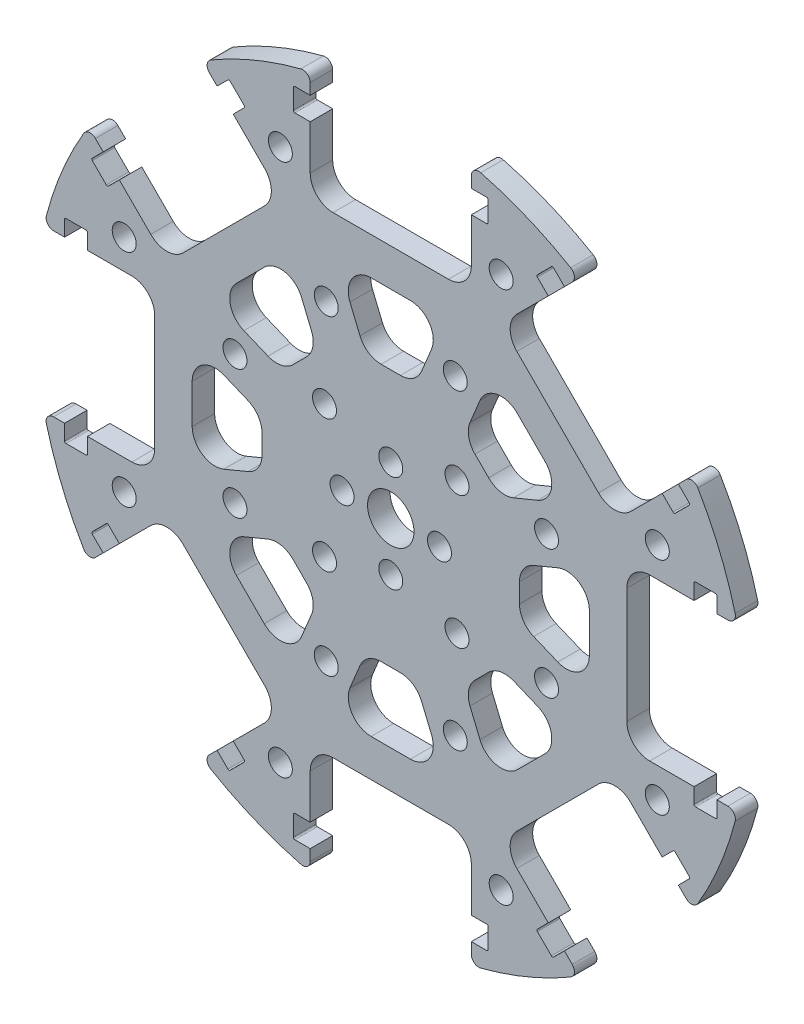
SolidWorks part; units mm, degrees
note: '?' marks a value the reader was unsure of.
material "5052-H34"
ref_plane "正面" through (0, 0, 0) normal (0, 0, 1) x (1, 0, 0)
ref_plane "平面" through (0, 0, 0) normal (0, 1, 0) x (1, 0, 0)
ref_plane "右側面" through (0, 0, 0) normal (1, 0, 0) x (0, 0, -1)
sketch "ｽｹｯﾁ1" plane through (0, 0, 0) normal (0, 0, 1) x (1, 0, 0)
  circle A0 centre (0, 0) radius 47.5
  dimension "D1" = 95
extrude "ﾎﾞｽ - 押し出し1" add sketch "ｽｹｯﾁ1" along normal blind 3
sketch "ｽｹｯﾁ2" plane through (0, 0, 3) normal (0, 0, 1) x (1, 0, 0)
  line L0 (0, 0) -> (0, 47.5) construction
  line L1 (-10.75, 43.525) -> (-10.75, 52.5)
  line L2 (-10.75, 31.5) -> (10.75, 31.5)
  line L3 (-10.75, 31.5) -> (-10.75, 40.475)
  line L4 (-10.75, 52.5) -> (10.75, 52.5)
  line L5 (10.75, 31.5) -> (10.75, 40.475)
  line L6 (-10.75, 31.5) -> (10.75, 52.5) construction
  line L7 (-10.75, 52.5) -> (10.75, 31.5) construction
  line L8 (-13, 43.525) -> (-10.75, 43.525)
  line L9 (-13, 43.525) -> (-13, 40.475)
  line L10 (-13, 40.475) -> (-10.75, 40.475)
  line L11 (13, 43.525) -> (13, 40.475)
  line L12 (-13, 43.525) -> (13, 40.475) construction
  line L13 (-13, 40.475) -> (13, 43.525) construction
  line L14 (10.75, 43.525) -> (10.75, 52.5)
  line L15 (10.75, 43.525) -> (13, 43.525)
  line L17 (10.75, 40.475) -> (13, 40.475)
  circle A0 centre (0, 0) radius 47.5 construction
  point P5 (0, 42)
  point P10 (0, 42)
  dimension "D1" = 42
  dimension "D2" = 21.5
  dimension "D3" = 21
  dimension "D4" = 3.05
  dimension "D5" = 26
extrude "ｶｯﾄ - 押し出し1" cut sketch "ｽｹｯﾁ2" against normal through all
sketch "ｽｹｯﾁ3" plane through (0, 0, 3) normal (0, 0, 1) x (1, 0, 0)
  line L1 (-8.8388, -8.8388) -> (8.8388, -8.8388) construction
  line L2 (-8.8388, -8.8388) -> (-8.8388, 8.8388) construction
  line L3 (-8.8388, 8.8388) -> (8.8388, 8.8388) construction
  line L4 (8.8388, -8.8388) -> (8.8388, 8.8388) construction
  line L5 (-8.8388, -8.8388) -> (8.8388, 8.8388) construction
  line L6 (-8.8388, 8.8388) -> (8.8388, -8.8388) construction
  circle A0 centre (0, 0) radius 3.1
  circle A1 centre (0, 0) radius 6.5 construction
  circle A2 centre (0, 6.5) radius 1.6
  circle A3 centre (6.5, 0) radius 1.6
  circle A4 centre (0, -6.5) radius 1.6
  circle A5 centre (-6.5, 0) radius 1.6
  circle A6 centre (0, 0) radius 12.5 construction
  circle A7 centre (8.8388, 8.8388) radius 1.6
  circle A8 centre (8.8388, -8.8388) radius 1.6
  circle A9 centre (-8.8388, -8.8388) radius 1.6
  circle A10 centre (-8.8388, 8.8388) radius 1.6
  dimension "D1" = 6.2
  dimension "D2" = 13
  dimension "D3" = 3.2
  dimension "D5" = 25
  dimension "D6" = 3.2
  dimension "D4" = 4
  dimension "D7" = 4
extrude "ｶｯﾄ - 押し出し2" cut sketch "ｽｹｯﾁ3" against normal through all and the other way through all
sketch "ｽｹｯﾁ4" plane through (0, 0, 3) normal (0, 0, 1) x (1, 0, 0)
  line L0 (0, 31.5) -> (0, 0) construction
  line L1 (-10.75, 31.5) -> (10.75, 31.5) construction
  line L2 (0, 0) -> (14.7333, 35.5694) construction
  circle A0 centre (0, 0) radius 22.5 construction
  circle A1 centre (0, 0) radius 38.5 construction
  circle A2 centre (14.7333, 35.5694) radius 1.6
  circle A3 centre (8.6104, 20.7873) radius 1.6
  dimension "D1" = 45
  dimension "D2" = 77
  dimension "D4" = 3.2
  dimension "D3" = 22.5
extrude "ｶｯﾄ - 押し出し3" cut sketch "ｽｹｯﾁ4" against normal through all
sketch "ｽｹｯﾁ5" plane through (0, 0, 3) normal (0, 0, 1) x (1, 0, 0)
  line L0 (0, 0) -> (14.7333, 35.5694) construction
  line L1 (-10.75, 31.5) -> (10.75, 31.5) construction
  line L2 (-10.75, 31.5) -> (10.75, 31.5) construction
  line L3 (-7.1883, 26.5) -> (7.1883, 26.5)
  line L4 (-3.3281, 17.1806) -> (-7.1883, 26.5)
  line L5 (0, 31.5) -> (0, 0) construction
  line L6 (-10.75, 26.5) -> (10.75, 26.5) construction
  line L9 (-3.3281, 17.1806) -> (3.3281, 17.1806)
  line L10 (3.3281, 17.1806) -> (7.1883, 26.5)
  circle A0 centre (0, 0) radius 17.5 construction
  dimension "D3" = 35
  dimension "D2" = 7
  dimension "D1" = 5
extrude "ｶｯﾄ - 押し出し4" cut sketch "ｽｹｯﾁ5" against normal through all and the other way through all
fillet "ﾌｨﾚｯﾄ1" radius 1 2 edges at (10.75, 46.2676, 1.5) (-10.75, 46.2676, 1.5)
fillet "ﾌｨﾚｯﾄ2" radius 0.2 4 edges at (13, 43.525, 1.5) (13, 40.475, 1.5) (-13, 43.525, 1.5) (-13, 40.475, 1.5)
fillet "ﾌｨﾚｯﾄ3" radius 3.05 2 edges at (10.75, 31.5, 1.5) (-10.75, 31.5, 1.5)
fillet "ﾌｨﾚｯﾄ4" radius 3.05 4 edges at (7.1883, 26.5, 1.5) (3.3281, 17.1806, 1.5) (-3.3281, 17.1806, 1.5) (-7.1883, 26.5, 1.5)
ref_axis "軸1" through (0, 0, 0) along (0, 0, 1)?
pattern_circular "円形ﾊﾟﾀｰﾝ1" count 8 over 360 about axis through (0, 0, 0) along (0, 0, 1) of "ｶｯﾄ - 押し出し1", "ﾌｨﾚｯﾄ1", "ｶｯﾄ - 押し出し4", "ｶｯﾄ - 押し出し3", "ﾌｨﾚｯﾄ2", "ﾌｨﾚｯﾄ3", "ﾌｨﾚｯﾄ4"
